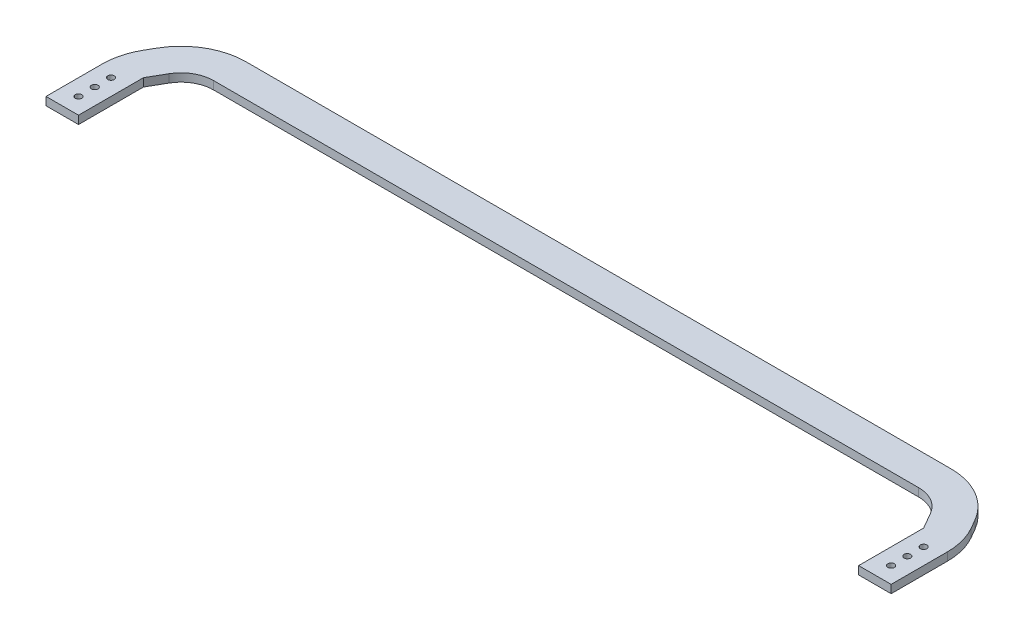
SolidWorks part; units mm, degrees
material "6061-T6 (SS)"
ref_plane "Front" through (0, 0, 0) normal (0, 0, 1) x (1, 0, 0)
ref_plane "Top" through (0, 0, 0) normal (0, 1, 0) x (1, 0, 0)
ref_plane "Right" through (0, 0, 0) normal (1, 0, 0) x (0, 0, -1)
sketch "Sketch1" plane through (0, 0, 0) normal (0, 1, 0) x (1, 0, 0)
  line L0 (-304.8, -50.8) -> (-304.8, 0)
  line L1 (304.8, 0) -> (304.8, -50.8)
  line L2 (304.8, -50.8) -> (330.2, -50.8)
  line L3 (0, 0) -> (0, -66.2098) construction
  line L4 (-304.8, -50.8) -> (-330.2, -50.8)
  line L5 (-330.2, -50.8) -> (-330.2, -6.8059)
  line L6 (330.2, -6.8059) -> (330.2, -50.8)
  line L7 (-304.8, 0) -> (-297.4677, 12.7)
  line L8 (-275.4706, 25.4) -> (275.4706, 25.4)
  line L9 (-304.8, 0) -> (304.8, 0) construction
  line L10 (297.4677, 12.7) -> (304.8, 0)
  line L11 (323.3941, 18.5941) -> (319.4647, 25.4)
  line L12 (275.4706, 50.8) -> (-275.4706, 50.8)
  line L13 (-319.4647, 25.4) -> (-323.3941, 18.5941)
  line L14 (330.2, 6.8059) -> (330.2, -50.8) construction
  line L15 (-330.2, -50.8) -> (-330.2, 6.8059) construction
  arc A6 (288.928, 9.9217) -> (304.8, 0) centre (284.3476, -15.0619) cw construction
  arc A7 (-330.2, 6.8059) -> (-316.3116, 28.5581) centre (-146.1041, -95.4263) cw construction
  arc A8 (-316.3116, 28.5581) -> (293.5083, 34.9053) centre (4.9476, -1539.0619) cw construction
  arc A9 (293.5083, 34.9053) -> (330.2, 6.8059) centre (284.3476, -15.0619) cw construction
  arc A10 (-304.8, 0) -> (-301.2394, 5.6855) centre (-146.1041, -95.4263) cw construction
  arc A11 (-301.2394, 5.6855) -> (288.928, 9.9217) centre (4.9476, -1539.0619) cw construction
  arc A12 (323.3941, 18.5941) -> (330.2, -6.8059) centre (279.4, -6.8059) cw
  arc A13 (319.4647, 25.4) -> (275.4706, 50.8) centre (275.4706, 0) ccw
  arc A14 (-330.2, -6.8059) -> (-323.3941, 18.5941) centre (-279.4, -6.8059) cw
  arc A15 (-275.4706, 50.8) -> (-319.4647, 25.4) centre (-275.4706, 0) ccw
  arc A16 (275.4706, 25.4) -> (297.4677, 12.7) centre (275.4706, 0) cw
  arc A17 (-297.4677, 12.7) -> (-275.4706, 25.4) centre (-275.4706, 0) cw
  dimension "D4" = 30
  dimension "D8" = 50.8
  dimension "D9" = 25.4
  dimension "D1" = 609.6
  dimension "D2" = 50.8
  dimension "D5" = 25.4
  dimension "D6" = 25.4
  dimension "D7" = 25.4
  dimension "D3" = 25.4
extrude "Boss-Extrude1" add sketch "Sketch1" along normal blind 6.35
hole_wizard "#10 Clearance Hole1" positions "Sketch2" profile "Sketch3" hole size "#10" standard "ANSI Inch" end condition through all
sketch "Sketch2" plane through (0, 6.35, 0) normal (0, 1, 0) x (1, 0, 0)
  line L3 (-330.2, -50.8) -> (-317.5, -38.1) construction
  line L4 (-317.5, -38.1) -> (-317.5, -25.4) construction
  line L5 (-317.5, -25.4) -> (-317.5, -12.7) construction
  line L6 (-317.5, -12.7) -> (-304.8, 0) construction
  line L8 (0, 0) -> (0, -50.8) construction
  point P0 (-317.5, -38.1)
  point P2 (-317.5, -25.4)
  point P4 (-317.5, -12.7)
  point P29 (317.5, -12.7)
  point P30 (317.5, -25.4)
  point P31 (317.5, -38.1)
  dimension "D1" = 12.7
sketch "Sketch3" plane through (-317.5, 6.35, 38.1) normal (1, 0, 0) x (0, 0, 1)
  line L0 (0, 0) -> (0, 6.35)
  line L1 (0, 6.35) -> (2.5527, 6.35)
  line L2 (2.5527, 6.35) -> (2.5527, 0)
  line L5 (2.5527, 0) -> (0, 0)
  line L11 (0, -6.35) -> (0, 107.95) construction
  dimension "Thru Hole Dia." = 5.1054
  dimension "Thru Hole Depth" = 6.35
